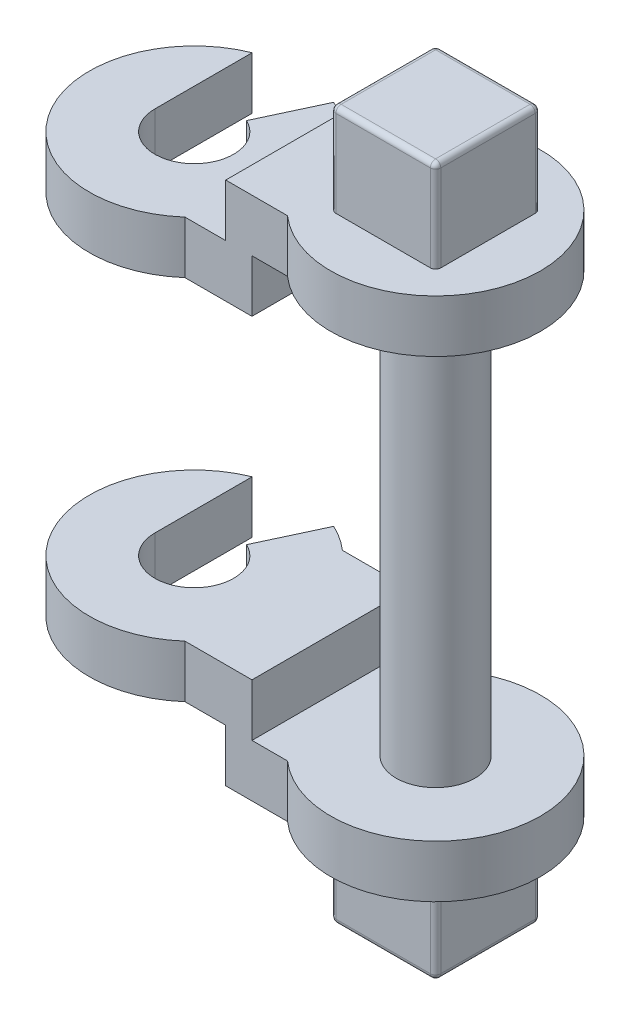
SolidWorks part; units mm, degrees
ref_plane "前视基准面" through (0, 0, 0) normal (0, 0, 1) x (1, 0, 0)
ref_plane "上视基准面" through (0, 0, 0) normal (0, 1, 0) x (1, 0, 0)
ref_plane "右视基准面" through (0, 0, 0) normal (1, 0, 0) x (0, 0, -1)
sketch "草图1" plane through (0, 0, 0) normal (0, 1, 0) x (1, 0, 0)
  circle A0 centre (0, 0) radius 0.75
extrude "凸台-拉伸1" add sketch "草图1" along normal blind 4 and the other way blind 4
sketch "草图2" plane through (0, 4, 0) normal (0, 1, 0) x (-1, 0, 0)
  circle A0 centre (0, 0) radius 2
extrude "凸台-拉伸2" add sketch "草图2" along normal blind 1
sketch "草图3" plane through (0, -4, 0) normal (0, -1, 0) x (1, 0, 0)
  circle A0 centre (0, 0) radius 2
extrude "凸台-拉伸3" add sketch "草图3" along normal blind 1
sketch "草图4" plane through (0, 5, 0) normal (0, 1, 0) x (-1, 0, 0)
  line L1 (-1, -1) -> (1, -1)
  line L2 (-1, -1) -> (-1, 1)
  line L3 (-1, 1) -> (1, 1)
  line L4 (1, -1) -> (1, 1)
extrude "凸台-拉伸4" add sketch "草图4" along normal blind 1.75
sketch "草图5" plane through (0, -5, 0) normal (0, -1, 0) x (1, 0, 0)
  line L1 (-1, -1) -> (1, -1)
  line L2 (-1, -1) -> (-1, 1)
  line L3 (-1, 1) -> (1, 1)
  line L4 (1, -1) -> (1, 1)
extrude "凸台-拉伸5" add sketch "草图5" along normal blind 1.75
sketch "草图6" plane through (0, 5, 0) normal (0, 1, 0) x (-1, 0, 0)
  line L1 (1, -1.5) -> (2.5, -1.5)
  line L2 (1, -1.5) -> (1, 1.5)
  line L3 (1, 1.5) -> (2.5, 1.5)
  line L4 (2.5, -1.5) -> (2.5, 1.5)
extrude "凸台-拉伸6" add sketch "草图6" against normal up to surface (1 mm away) up to face at (0, 4, 0.75)
sketch "草图7" plane through (0, -5, 0) normal (0, -1, 0) x (1, 0, 0)
  line L1 (-1, -1.5) -> (-2.5, -1.5)
  line L2 (-1, -1.5) -> (-1, 1.5)
  line L3 (-1, 1.5) -> (-2.5, 1.5)
  line L4 (-2.5, -1.5) -> (-2.5, 1.5)
extrude "凸台-拉伸8" add sketch "草图7" against normal up to surface (1 mm away) up to face at (0, -4, -0.75)
sketch "草图8" plane through (-2.5, 0, 0) normal (-1, 0, 0) x (0, 0, 1)
  line L1 (-1.5, 5) -> (1.5, 5)
  line L2 (-1.5, 5) -> (-1.5, 3)
  line L3 (-1.5, 3) -> (1.5, 3)
  line L4 (1.5, 5) -> (1.5, 3)
  line L5 (-1.5, -5) -> (1.5, -5)
  line L6 (-1.5, -5) -> (-1.5, -3)
  line L7 (-1.5, -3) -> (1.5, -3)
  line L8 (1.5, -5) -> (1.5, -3)
extrude "凸台-拉伸9" add sketch "草图8" against normal blind 0.5
sketch "草图9" plane through (0, 3, 0) normal (0, -1, 0) x (1, 0, 0)
  line L1 (-2.5, -1.5) -> (-3.2771, -1.5)
  line L2 (-2.5, -1.5) -> (-2.5, 1.5)
  line L3 (-2.5, 1.5) -> (-3.2771, 1.5)
  arc A0 (-3.2771, 1.5) -> (-3.2771, -1.5) centre (-4.6, 0) ccw
extrude "凸台-拉伸10" add sketch "草图9" against normal blind 1
extrude "凸台-拉伸11" add sketch "草图9<2>" along normal blind 1 from offset 6
sketch "草图9<2>" plane through (0, 3, 0) normal (0, -1, 0) x (1, 0, 0) same geometry as "草图9"
sketch "草图10" plane through (0, 4, 0) normal (0, 1, 0) x (-1, 0, 0)
  line L0 (5.35, 0) -> (5.35, -1.854)
  line L1 (4.283, -0.6797) -> (3.7548, -1.8126)
  arc A0 (5.35, 0) -> (4.283, -0.6797) centre (4.6, 0) ccw
  arc A1 (3.7548, -1.8126) -> (5.35, -1.854) centre (4.6, 0) ccw
extrude "切除-拉伸1" cut sketch "草图10" against normal through all
fillet "圆角1" radius 0.1 16 edges at (0, -6.75, 1) (1, -6.75, 0) (0, -6.75, -1) (-1, -6.75, 0) (0, 6.75, 1) (-1, 6.75, 0) (0, 6.75, -1) (1, 6.75, 0) (1, -5.875, 1) (1, -5.875, -1) (-1, -5.875, 1) (-1, -5.875, -1) (-1, 5.875, -1) (1, 5.875, -1) (-1, 5.875, 1) (1, 5.875, 1)
